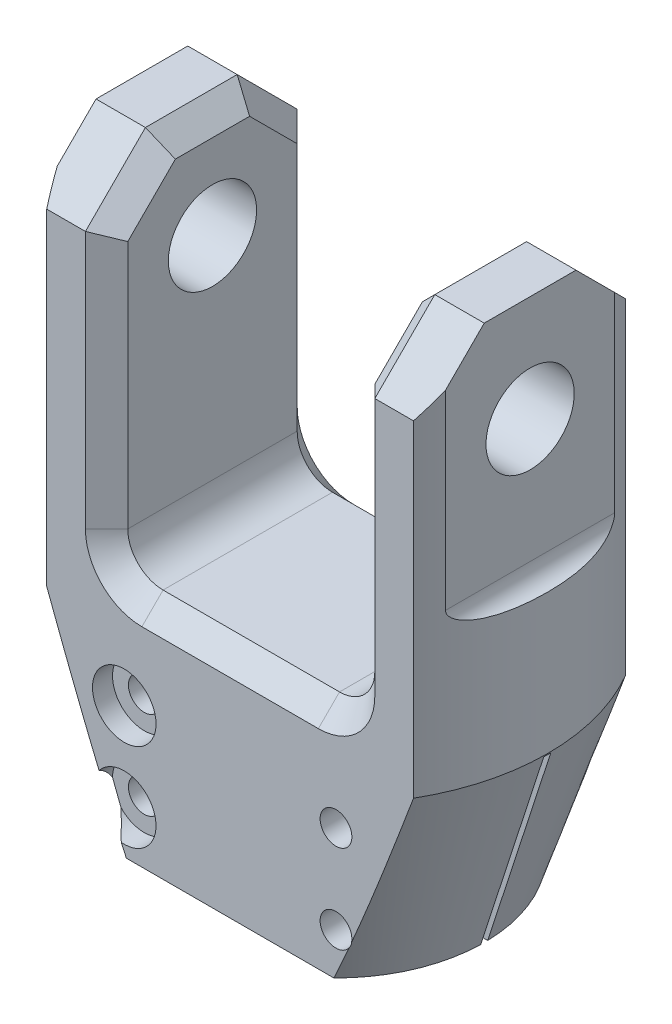
SolidWorks part; units mm, degrees
ref_plane "前基準面" through (0, 0, 0) normal (0, 0, 1) x (1, 0, 0)
ref_plane "上基準面" through (0, 0, 0) normal (0, 1, 0) x (1, 0, 0)
ref_plane "右基準面" through (0, 0, 0) normal (1, 0, 0) x (0, 0, -1)
sketch "草圖1" plane through (0, 0, 0) normal (0, 1, 0) x (1, 0, 0)
  circle A0 centre (0, 0) radius 60
  dimension "D1" = 120
extrude "填料-伸長1" add sketch "草圖1" along normal blind 165
sketch "草圖2" plane through (0, 0, 0) normal (1, 0, 0) x (0, 0, -1)
  line L0 (0, -1000) -> (0, 49000) construction
  line L1 (-60, 0) -> (60, 0) construction
  line L3 (60, 165) -> (-60, 165) construction
  line L4 (-30, 165) -> (-60, 165)
  line L5 (-30, 165) -> (-30, 0)
  line L6 (-30, 0) -> (-60, 0)
  line L7 (-60, 165) -> (-60, 0)
  line L9 (30, 165) -> (60, 165)
  line L10 (30, 165) -> (30, 0)
  line L11 (30, 0) -> (60, 0)
  line L12 (60, 165) -> (60, 0)
  point P5 (0, 0)
  dimension "D1" = 60
extrude "除料-伸長1" cut sketch "草圖2" against normal mid plane 165
hole_wizard "Ø3.0 (3) 直徑孔1" positions "草圖5" profile "草圖4" hole size "Ø3.0" standard "Ansi 公制"
sketch "草圖5" plane through (0, 0, 0) normal (0, -1, 0) x (1, 0, 0)
  point P0 (0, 0)
sketch "草圖4" plane through (0, 0, 0) normal (1, 0, 0) x (0, 0, -1)
  line L0 (0, 0) -> (0, 59.0387)
  line L1 (0, 59.0387) -> (21.7, 46)
  line L2 (21.7, 46) -> (21.7, 0)
  line L5 (21.7, 0) -> (0, 0)
  line L10 (0, 59.0387) -> (-21.7, 46) construction
  line L11 (0, -6.35) -> (0, 107.95) construction
  dimension "鑽孔直徑" = 43.4
  dimension "鑽孔深度" = 46
  dimension "導頭角度" = 118
sketch "草圖6" plane through (0, 0, 30) normal (0, 0, 1) x (1, 0, 0)
  line L0 (0, -1000) -> (0, 49000) construction
  line L1 (51.9615, 0) -> (-51.9615, 0) construction
  line L2 (-51.9615, 165) -> (51.9615, 165) construction
  line L3 (-35, 165) -> (35, 165)
  line L4 (-35, 165) -> (-35, 65)
  line L5 (-35, 65) -> (35, 65)
  line L6 (35, 165) -> (35, 65)
  point P5 (0, 0)
  dimension "D1" = 70
  dimension "D2" = 100
extrude "除料-伸長2" cut sketch "草圖6" against normal through all
sketch "草圖7" plane through (0, 0, 0) normal (0, 0, 1) x (1, 0, 0)
  line L0 (0, -1000) -> (0, 49000) construction
  line L1 (-60, 165) -> (-55, 165)
  line L2 (-60, 165) -> (-60, 95)
  line L3 (-60, 95) -> (-55, 95)
  line L4 (-55, 165) -> (-55, 95)
  line L5 (60, 165) -> (55, 165)
  line L6 (60, 165) -> (60, 95)
  line L7 (60, 95) -> (55, 95)
  line L8 (55, 165) -> (55, 95)
  dimension "D1" = 110
  dimension "D2" = 70
extrude "除料-伸長3" cut sketch "草圖7" against normal mid plane 165
hole_wizard "M27x2.0 螺紋孔1" positions "草圖9" profile "草圖8" tap size "M27x2.0" standard "ISO" end condition through all
sketch "草圖9" plane through (-55, 0, 0) normal (-1, 0, 0) x (0, 0, 1)
  line L0 (0, -835) -> (0, 49165) construction
  line L1 (-23.9792, 165) -> (23.9792, 165) construction
  point P0 (0, 135)
  point P7 (0, 165)
  dimension "D1" = 30
sketch "草圖8" plane through (-55, 135, 0) normal (0, 1, 0) x (0, 0, 1)
  line L0 (0, 0) -> (0, 115)
  line L1 (0, 115) -> (12.5, 115)
  line L2 (12.5, 115) -> (12.5, 0)
  line L5 (12.5, 0) -> (0, 0)
  line L11 (0, -6.35) -> (0, 107.95) construction
  dimension "貫穿螺孔鑽直徑" = 25
  dimension "貫穿螺孔鑽深度" = 115
cosmetic thread "鑽孔螺紋1" parameters "D2"=27
fillet "圓角1" radius 10 2 edges at (35, 65, 0) (-35, 65, 0)
chamfer "導角1" distance 17 angle 45 4 edges at (43.4808, 165, -30) (43.4808, 165, 30) (-43.4808, 165, -30) (-43.4808, 165, 30)
chamfer "導角2" distance 6 angle 45 16 edges at (-35, 111.5, -30) (-32.0711, 67.9289, -30) (0, 65, -30) (32.0711, 67.9289, -30) (35, 111.5, -30) (35, 156.5, -21.5) (35, 165, 0) (35, 156.5, 21.5) (35, 111.5, 30) (32.0711, 67.9289, 30) (0, 65, 30) (-32.0711, 67.9289, 30) (-35, 156.5, -21.5) (-35, 111.5, 30) (-35, 156.5, 21.5) (-35, 165, 0)
fillet "圓角2" radius 5 2 edges at (55, 95, 0) (-55, 95, 0)
sketch "草圖10" plane through (0, 0, 0) normal (0, 0, 1) x (1, 0, 0)
  line L0 (0, -1000) -> (0, 49000) construction
  line L1 (51.9615, 0) -> (-51.9615, 0) construction
  line L2 (-42, 0) -> (-63.1198, 65)
  line L3 (-63.1198, 65) -> (-77.8036, 65)
  line L4 (-77.8036, 65) -> (-77.8036, 0)
  line L5 (-77.8036, 0) -> (-42, 0)
  point P5 (0, 0)
  dimension "D1" = 84
  dimension "D2" = 65
  dimension "D3" = 108
revolve "除料-旋轉1" cut sketch "草圖10" angle 360 about L0
sketch "草圖11" plane through (0, 0, 0) normal (0, -1, 0) x (1, 0, 0)
  line L0 (-1000, 0) -> (49000, 0) construction
  line L3 (-67.5643, 1) -> (72.6723, 1)
  line L4 (-67.5643, 1) -> (-67.5643, -1)
  line L5 (-67.5643, -1) -> (72.6723, -1)
  line L6 (72.6723, 1) -> (72.6723, -1)
  dimension "D1" = 2
extrude "除料-伸長4" cut sketch "草圖11" against normal blind 55
hole_wizard "M8 六角頭螺栓的柱孔1" positions "草圖13" profile "草圖12" counterbore size "M8" standard "Ansi 公制" end condition through all
sketch "草圖13" plane through (0, 0, 30) normal (0, 0, 1) x (1, 0, 0)
  line L0 (0, 127.8535) -> (0, 58.4217) construction
  point P0 (-30, 37.1311)
  point P1 (-30, 12.1311)
  dimension "D1" = 25
  dimension "D2" = 30
sketch "草圖12" plane through (-30, 37.1311, 30) normal (1, 0, 0) x (0, -1, 0)
  line L0 (0, 0) -> (0, 60)
  line L1 (0, 60) -> (4.5, 60)
  line L3 (4.5, 60) -> (4.5, 5.68)
  line L4 (4.5, 5.68) -> (9.005, 5.68)
  line L5 (9.005, 5.68) -> (9.005, 0)
  line L7 (9.005, 0) -> (0, 0)
  line L11 (0, -6.35) -> (0, 107.95) construction
  dimension "貫穿孔直徑" = 9
  dimension "貫穿孔深度" = 60
  dimension "柱孔直徑" = 18.01
  dimension "柱孔深度" = 5.68
pattern_circular "環狀複製排列1" count 2 over 360 about axis through (0, 165, 0) along (0, -1, 0) of "M8 六角頭螺栓的柱孔1"
